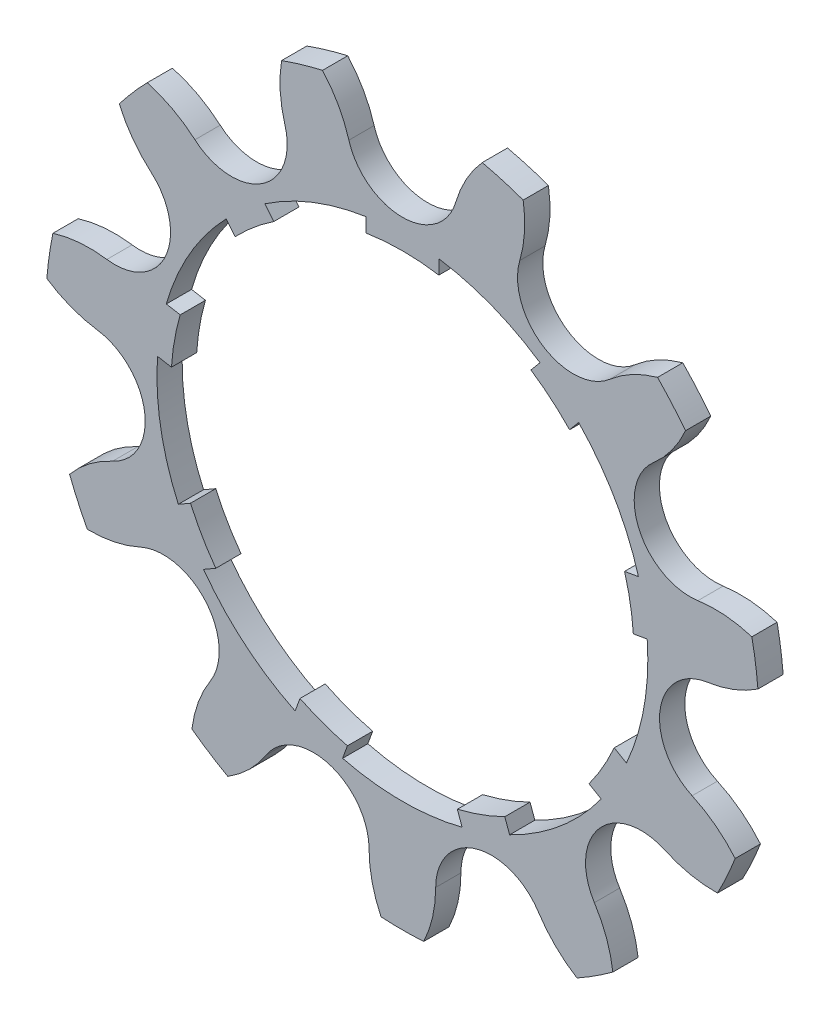
SolidWorks part; units mm, degrees
ref_plane "Alzado" through (0, 0, 0) normal (0, 0, 1) x (1, 0, 0)
ref_plane "Planta" through (0, 0, 0) normal (0, 1, 0) x (1, 0, 0)
ref_plane "Vista lateral" through (0, 0, 0) normal (1, 0, 0) x (0, 0, -1)
sketch "Sk_Disco" plane through (0, 0, 0) normal (0, 0, 1) x (1, 0, 0)
  line L0 (2.6, 17.3058) -> (2.6, 16.2939)
  line L1 (-2.6, 16.2939) -> (-2.6, 17.3058)
  line L2 (-9.8102, 14.4917) -> (-9.1638, 13.7213)
  line L3 (-11.9216, 11.4073) -> (-12.568, 12.1777)
  line L4 (-16.8302, 4.7954) -> (-15.8398, 4.6207)
  line L5 (-16.4649, 1.0754) -> (-17.4553, 1.2501)
  line L6 (-15.9751, -7.1447) -> (-15.1041, -6.6419)
  line L7 (-13.3041, -9.7596) -> (-14.1751, -10.2624)
  line L8 (-7.6451, -15.7418) -> (-7.3011, -14.7968)
  line L9 (-3.9182, -16.028) -> (-4.2622, -16.973)
  line L10 (4.2622, -16.973) -> (3.9182, -16.028)
  line L11 (7.3011, -14.7968) -> (7.6451, -15.7418)
  line L12 (14.1751, -10.2624) -> (13.3041, -9.7596)
  line L13 (15.1041, -6.6419) -> (15.9751, -7.1447)
  line L14 (17.4553, 1.2501) -> (16.4649, 1.0754)
  line L15 (15.8398, 4.6207) -> (16.8302, 4.7954)
  line L16 (12.568, 12.1777) -> (11.9216, 11.4073)
  line L17 (9.1638, 13.7213) -> (9.8102, 14.4917)
  circle A0 centre (0, 0) radius 25.4361
  arc A1 (2.6, 16.2939) -> (-2.6, 16.2939) centre (0, 0) ccw
  arc A2 (-2.6, 17.3058) -> (-9.8102, 14.4917) centre (0, 0) ccw
  arc A3 (-9.1638, 13.7213) -> (-11.9216, 11.4073) centre (0, 0) ccw
  arc A4 (-12.568, 12.1777) -> (-16.8302, 4.7954) centre (0, 0) ccw
  arc A5 (-15.8398, 4.6207) -> (-16.4649, 1.0754) centre (0, 0) ccw
  arc A6 (-17.4553, 1.2501) -> (-15.9751, -7.1447) centre (0, 0) ccw
  arc A7 (-15.1041, -6.6419) -> (-13.3041, -9.7596) centre (0, 0) ccw
  arc A8 (-14.1751, -10.2624) -> (-7.6451, -15.7418) centre (0, 0) ccw
  arc A9 (-7.3011, -14.7968) -> (-3.9182, -16.028) centre (0, 0) ccw
  arc A10 (-4.2622, -16.973) -> (4.2622, -16.973) centre (0, 0) ccw
  arc A11 (3.9182, -16.028) -> (7.3011, -14.7968) centre (0, 0) ccw
  arc A12 (7.6451, -15.7418) -> (14.1751, -10.2624) centre (0, 0) ccw
  arc A13 (13.3041, -9.7596) -> (15.1041, -6.6419) centre (0, 0) ccw
  arc A14 (15.9751, -7.1447) -> (17.4553, 1.2501) centre (0, 0) ccw
  arc A15 (16.4649, 1.0754) -> (15.8398, 4.6207) centre (0, 0) ccw
  arc A16 (16.8302, 4.7954) -> (12.568, 12.1777) centre (0, 0) ccw
  arc A17 (11.9216, 11.4073) -> (9.1638, 13.7213) centre (0, 0) ccw
  arc A18 (9.8102, 14.4917) -> (2.6, 17.3058) centre (0, 0) ccw
  dimension "D1" = 50.8722
extrude "Disco" add sketch "Sk_Disco" along normal blind 1.8
sketch "Sk_Hueco" plane through (0, 0, 0) normal (0, 0, 1) x (1, 0, 0)
  line L0 (0, 0) -> (0, 22.5391) construction
  line L1 (0, 0) -> (-12.1856, 18.9611) construction
  line L2 (0, 0) -> (12.1856, 18.9611) construction
  line L3 (0, 22.5391) -> (-12.1856, 18.9611) construction
  line L4 (0, 22.5391) -> (12.1856, 18.9611) construction
  arc A0 (-3.814, 21.4192) -> (3.814, 21.4192) centre (0, 22.5391) ccw
  arc A1 (-3.814, 21.4192) -> (-7.5764, 26.3693) centre (-12.1856, 18.9611) ccw
  arc A2 (7.5764, 26.3693) -> (3.814, 21.4192) centre (12.1856, 18.9611) ccw
  arc A3 (7.5764, 26.3693) -> (-7.5764, 26.3693) centre (0, 0) ccw
  dimension "D6" = 3.975
  dimension "D7" = 27.4361
  dimension "D1" = 22.5391
  dimension "D2" = 22.5391
  dimension "D3" = 22.5391
  dimension "D4" = 32.727
  dimension "D5" = 32.727
extrude "Hueco_diente" cut sketch "Sk_Hueco" along normal through all
ref_axis "Eje_pinon" through (0, 0, -0.09) along (0, 0, 1)
pattern_circular "Matriz_dientes" count 11 over 360 about axis through (0, 0, -0.09) along (0, 0, 1) of "Hueco_diente"
equation "\"Z\"= 11"
equation "\"p\"= 12.7"
equation "\"Dr\"= 7.75"
equation "\"e\"= 1.8"
equation "\"D\"= \"p\" / sin ( 180 / \"Z\" )"
equation "\"De\"= \"p\" * ( 0.6 + 1 / tan ( 180 / \"Z\" ) )"
equation "\"Di\"= \"D\" - \"Dr\""
equation "\"Ang\"= 360 / \"Z\""
equation "\"D1@Sk_Disco\" = \"De\""
equation "\"D1@Disco\" = \"e\""
equation "\"D1@Sk_Hueco\" = \"D\" / 2"
equation "\"D2@Sk_Hueco\" = \"D\" / 2"
equation "\"D3@Sk_Hueco\" = \"D\" / 2"
equation "\"D4@Sk_Hueco\" = \"Ang\""
equation "\"D5@Sk_Hueco\" = \"Ang\""
equation "\"D6@Sk_Hueco\" = \"Dr\" / 2 + 0.1"
equation "\"D7@Sk_Hueco\" = \"De\" / 2 + 2"
equation "\"D1@Matriz_dientes\" = \"Z\""
